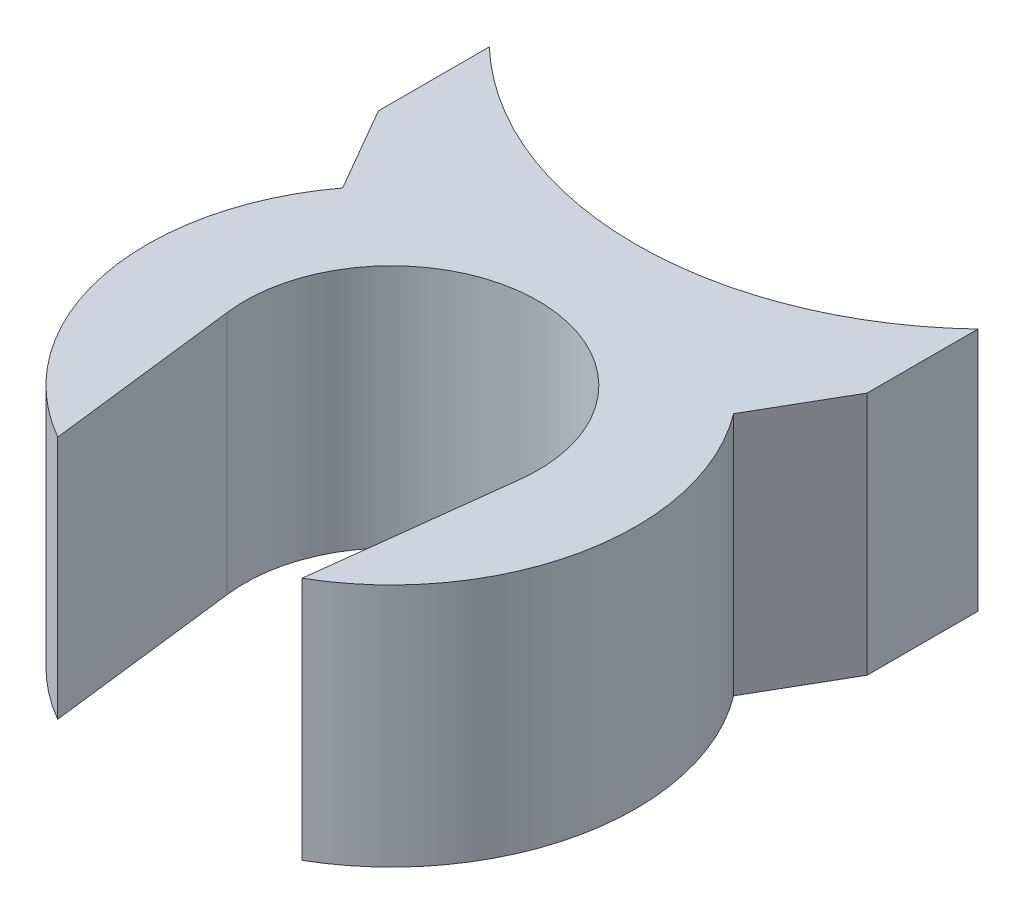
SolidWorks part; units mm, degrees
ref_plane "Front" through (0, 0, 0) normal (0, 0, 1) x (1, 0, 0)
ref_plane "Top" through (0, 0, 0) normal (0, 1, 0) x (1, 0, 0)
ref_plane "Right" through (0, 0, 0) normal (1, 0, 0) x (0, 0, -1)
sketch "Croquis1" plane through (0, 0, 0) normal (0, 1, 0) x (1, 0, 0)
  line L0 (0, 0) -> (0, 7) construction
  line L2 (-5, 7) -> (-5, 3)
  line L3 (-5, 3) -> (-4, 3)
  line L4 (5, 7) -> (5, 3)
  line L5 (4, 3) -> (5, 3)
  circle A0 centre (0, 0) radius 3
  arc A1 (-4, 3) -> (4, 3) centre (0, 0) ccw
  arc A2 (-5, 7) -> (5, 7) centre (0, 12.25) ccw
  dimension "D1" = 6
  dimension "D2" = 10
  dimension "D3" = 7
  dimension "D4" = 4
  dimension "D5" = 10
extrude "Saliente-Extruir1" add sketch "Croquis1" along normal blind 5
sketch "Croquis2" plane through (0, 5, 0) normal (0, 1, 0) x (1, 0, 0)
  line L0 (0, 0) -> (0, -5) construction
  line L1 (-2.5, -4.3301) -> (-2.9818, -0.3301)
  line L2 (2.5, -4.3301) -> (2.9818, -0.3301)
  arc A0 (-4, 3) -> (4, 3) centre (0, 0) ccw construction
  circle A1 centre (0, 0) radius 3 construction
  arc A2 (-2.9818, -0.3301) -> (2.9818, -0.3301) centre (0, 0) ccw
  arc A3 (-2.5, -4.3301) -> (4, 3) centre (0, 0) ccw
  point P10 (-2.6369, -1.4307)
  point P13 (-2.8284, -1)
  point P14 (-3, -4)
  point P15 (-3, -4)
  arc M7 (-4, 3) -> (4, 3) centre (0, 0) ccw
  circle M10 centre (0, 0) radius 3
  dimension "D1" = 2.5
  dimension "D2" = 4
extrude "Cortar-Extruir1" cut sketch "Croquis2" against normal blind 10 contours L0 A3 L2 M10 | L0 A2 L1 M7 region at (0, 5, 1.0557)
sketch "Croquis3" plane through (0, 5, 0) normal (0, 1, 0) x (1, 0, 0)
  line L0 (4, 3) -> (5, 4.7321)
  line L1 (5, 3) -> (5, 7) construction
  line L2 (0, 3) -> (0, 5) construction
  line L3 (-4, 3) -> (-5, 4.7321)
  line L4 (4, 3) -> (5, 3) construction
  line L5 (-5, 3) -> (-4, 3) construction
  line L6 (-5, 7) -> (-5, 3) construction
  line L7 (5, 3) -> (5, 4.7321)
  line L8 (4, 3) -> (5, 3)
  line L9 (-5, 3) -> (-4, 3)
  line L10 (-5, 4.7321) -> (-5, 3)
  arc A0 (2.9749, -0.3873) -> (-2.9749, -0.3873) centre (0, 0) ccw construction
  arc A1 (-5, 7) -> (5, 7) centre (0, 12.25) ccw construction
  dimension "D1" = 2
extrude "Cortar-Extruir2" cut sketch "Croquis3" against normal blind 10
